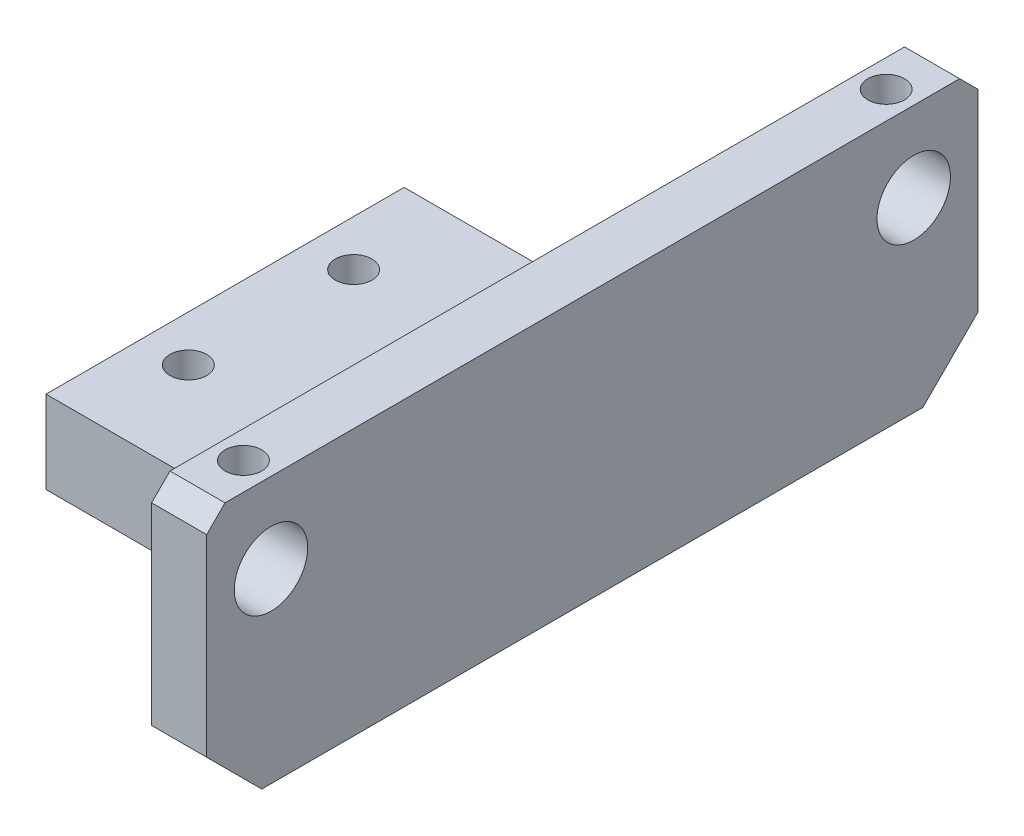
SolidWorks part; units mm, degrees
ref_plane "Front Plane" through (0, 0, 0) normal (0, 0, 1) x (1, 0, 0)
ref_plane "Top Plane" through (0, 0, 0) normal (0, 1, 0) x (1, 0, 0)
ref_plane "Right Plane" through (0, 0, 0) normal (1, 0, 0) x (0, 0, -1)
sketch "Sketch1" plane through (0, 0, 0) normal (0, 1, 0) x (1, 0, 0)
  line L0 (0, -9) -> (0, 9) construction
  line L1 (-17, 19.5) -> (17, 19.5)
  line L2 (-17, 19.5) -> (-17, -19.5)
  line L3 (-17, -19.5) -> (17, -19.5)
  line L4 (17, 19.5) -> (17, -19.5)
  line L5 (-17, 19.5) -> (17, -19.5) construction
  line L6 (-17, -19.5) -> (17, 19.5) construction
  line L7 (-12, 0) -> (12, 0) construction
  circle A0 centre (-12, -9) radius 2
  circle A1 centre (12, -9) radius 2
  circle A2 centre (12, 9) radius 2
  circle A3 centre (-12, 9) radius 2
  point P0 (0, 0)
  point P11 (0, 0)
  point P15 (0, 0)
  dimension "D5" = 4
  dimension "D1" = 39
  dimension "D2" = 34
  dimension "D3" = 18
  dimension "D4" = 24
extrude "Boss-Extrude1" add sketch "Sketch1" along normal blind 5
sketch "Sketch2" plane through (0, 0, 0) normal (0, -1, 0) x (1, 0, 0)
  line L4 (17, 42) -> (17, -42)
  line L6 (17, -42) -> (23, -42)
  line L7 (17, 42) -> (23, 42)
  line L8 (23, -42) -> (23, 42)
  point P7 (17, 0)
  dimension "D1" = 84
extrude "Boss-Extrude2" add sketch "Sketch2" against normal blind 25
sketch "Sketch3" plane through (23, 0, 0) normal (1, 0, 0) x (0, 0, -1)
  line L0 (0, 5) -> (0, 24.033) construction
  line L1 (-35, 16.2752) -> (35, 16.2752) construction
  circle A2 centre (-35, 16.2752) radius 4
  circle A3 centre (35, 16.2752) radius 4
  point P6 (0, 16.2752)
  dimension "D3" = 8
  dimension "D4" = 8
  dimension "D1" = 5
  dimension "D2" = 70
extrude "Cut-Extrude2" cut sketch "Sketch3" against normal up to next
chamfer "Chamfer1" distance 2 angle 45 4 edges at (20, 25, 42) (20, 25, -42) (20, 0, -42) (20, 0, 42)
sketch "Sketch4" plane through (0, 25, 0) normal (0, 1, 0) x (1, 0, 0)
  line L0 (23, 0) -> (17, 0) construction
  line L1 (23, 40) -> (23, -40) construction
  line L2 (17, -19.5) -> (17, 19.5) construction
  line L3 (20, -35) -> (20, 35) construction
  circle A0 centre (20, 35) radius 2
  circle A1 centre (20, -35) radius 2
  point P9 (20, 0)
  dimension "D2" = 4
  dimension "D3" = 4
  dimension "D1" = 70
extrude "Cut-Extrude3" cut sketch "Sketch4" against normal blind 10
sketch "Sketch5" plane through (0, 0, 0) normal (0, -1, 0) x (1, 0, 0)
  line L8 (17, -19.5) -> (17, -40)
  line L9 (17, -40) -> (23, -40)
  line L10 (23, -40) -> (23, 40)
  line L11 (23, 40) -> (17, 40)
  line L12 (17, 40) -> (17, 19.5)
  line L13 (17, 19.5) -> (-17, 19.5)
  line L14 (-17, 19.5) -> (-17, -19.5)
  line L15 (-17, -19.5) -> (17, -19.5)
  line L16 (17, -19.5) -> (17, -40)
  line L17 (17, -40) -> (23, -40)
  line L18 (23, -40) -> (23, 40)
  line L19 (23, 40) -> (17, 40)
  line L20 (17, 40) -> (17, 19.5)
  line L21 (17, 19.5) -> (-17, 19.5)
  line L22 (-17, 19.5) -> (-17, -19.5)
  line L23 (-17, -19.5) -> (17, -19.5)
  dimension "D1" = 0
extrude "Boss-Extrude3" add sketch "Sketch5" along normal blind 4
sketch "Sketch6" plane through (0, -4, 0) normal (0, -1, 0) x (1, 0, 0)
  line L0 (-12, 0) -> (12, 0) construction
  line L1 (0, -9) -> (0, 9) construction
  circle A0 centre (-12, -9) radius 3.7
  circle A1 centre (12, -9) radius 3.7
  circle A2 centre (12, 9) radius 3.7
  circle A3 centre (-12, 9) radius 3.7
  point P4 (0, 0)
  point P8 (0, 0)
  dimension "D3" = 7.4
  dimension "D1" = 24
  dimension "D2" = 18
extrude "Cut-Extrude4" cut sketch "Sketch6" against normal blind 5
chamfer "Chamfer2" distance 4 angle 45 2 edges at (20, -4, 40) (20, -4, -40)
sketch "Sketch7" plane through (0, -4, 0) normal (0, -1, 0) x (1, 0, 0)
  line L0 (12, -15) -> (12, 15) construction
  line L2 (23, -36) -> (23, 36) construction
  circle A0 centre (12, 15) radius 1.35
  circle A1 centre (12, -15) radius 1.35
  point P4 (0, 0)
  dimension "D2" = 2.7
  dimension "D3" = 2.7
  dimension "D1" = 30
  dimension "D4" = 11
extrude "Cut-Extrude5" cut sketch "Sketch7" against normal up to next
